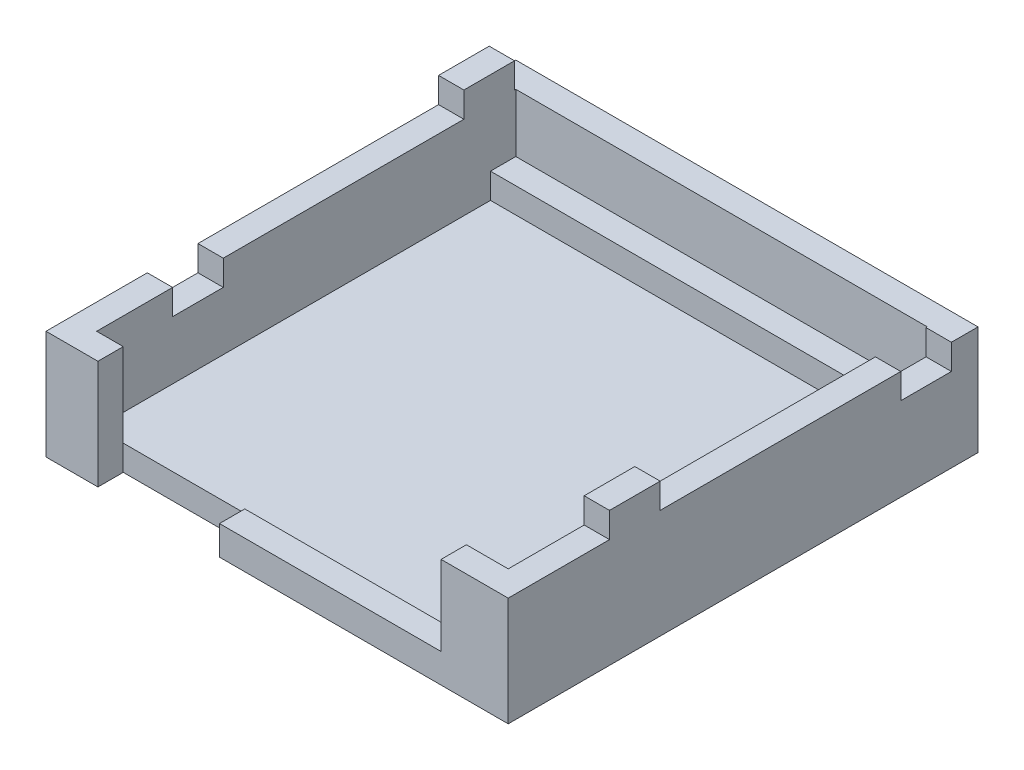
SolidWorks part; units mm, degrees
ref_plane "Front Plane" through (0, 0, 0) normal (0, 0, 1) x (1, 0, 0)
ref_plane "Top Plane" through (0, 0, 0) normal (0, 1, 0) x (1, 0, 0)
ref_plane "Right Plane" through (0, 0, 0) normal (1, 0, 0) x (0, 0, -1)
sketch "Sketch3" plane through (0, 0, 0) normal (0, 1, 0) x (1, 0, 0)
  line L1 (0, 0) -> (36.5, 0)
  line L2 (0, 0) -> (0, -37.1)
  line L3 (0, -37.1) -> (36.5, -37.1)
  line L4 (36.5, 0) -> (36.5, -37.1)
  dimension "D1" = 37.1
  dimension "D2" = 36.5
extrude "Shell" add sketch "Sketch3" along normal blind 8.6
sketch "Sketch4" plane through (0, 8.6, 0) normal (0, 1, 0) x (1, 0, 0)
  line L0 (36.5, 0) -> (0, 0) construction
  line L1 (2, -4) -> (34.5, -4)
  line L2 (2, -4) -> (2, -35.1)
  line L3 (2, -35.1) -> (34.5, -35.1)
  line L4 (34.5, -4) -> (34.5, -35.1)
  line L5 (36.5, -37.1) -> (36.5, 0) construction
  line L6 (0, 0) -> (0, -37.1) construction
  line L7 (0, -37.1) -> (36.5, -37.1) construction
  dimension "D1" = 4
  dimension "D2" = 2
  dimension "D3" = 2
  dimension "D4" = 2
extrude "Main Cavity" cut sketch "Sketch4" against normal offset from surface (6.6 mm away) 2 up to face at (18.25, 0, 18.55)
sketch "Sketch5" plane through (0, 8.6, 0) normal (0, 1, 0) x (1, 0, 0)
  line L0 (34.5, -35.1) -> (34.5, -4) construction
  line L1 (2, -4) -> (34.5, -4)
  line L2 (2, -4) -> (2, -2)
  line L3 (2, -2) -> (34.5, -2)
  line L4 (34.5, -4) -> (34.5, -2)
  dimension "D1" = 2
extrude "Support Shelf" cut sketch "Sketch5" against normal offset from surface (4.6 mm away) 2 up to face at (18.25, 2, 19.55)
sketch "Sketch6" plane through (0, 0, 37.1) normal (0, 0, 1) x (1, 0, 0)
  line L0 (0, 0) -> (36.5, 0) construction
  line L2 (31.2, 2.3) -> (31.2, 8.6)
  line L10 (13.7, 0) -> (4.1, 0)
  line L13 (4.1, 0) -> (4.1, 8.6)
  line L14 (0, 8.6) -> (0, 0) construction
  line L18 (13.7, 0) -> (13.7, 2.3)
  line L19 (13.7, 2.3) -> (31.2, 2.3)
  line L20 (31.2, 8.6) -> (4.1, 8.6)
  dimension "D1" = 4.1
  dimension "D6" = 9.6
extrude "Terminal Input" cut sketch "Sketch6" against normal up to surface (2 mm away) up to face at (18.25, 5.3, 35.1)
sketch "Sketch7" plane through (0, 8.6, 0) normal (0, 1, 0) x (1, 0, 0)
  line L0 (36.5, -37.1) -> (36.5, 0) construction
  line L1 (34.5, -25.1) -> (36.5, -25.1)
  line L2 (34.5, -25.1) -> (34.5, -29.1)
  line L3 (34.5, -29.1) -> (36.5, -29.1)
  line L4 (36.5, -25.1) -> (36.5, -29.1)
  line L5 (0, -2.1) -> (2, -2.1)
  line L6 (0, -2.1) -> (0, -6.1)
  line L7 (0, -6.1) -> (2, -6.1)
  line L8 (2, -2.1) -> (2, -6.1)
  line L9 (34.5, -35.1) -> (34.5, -2) construction
  line L10 (2, -2) -> (2, -35.1) construction
  line L11 (0, 0) -> (0, -37.1) construction
  line L12 (31.2, -37.1) -> (36.5, -37.1) construction
  line L14 (36.5, 0) -> (0, 0) construction
  dimension "D1" = 4
  dimension "D2" = 4
  dimension "D3" = 8
  dimension "D4" = 2.1
extrude "Male Tabs" add sketch "Sketch7" along normal blind 2
sketch "Sketch8" plane through (0, 8.6, 0) normal (0, 1, 0) x (1, 0, 0)
  line L0 (2, -2.1) -> (0, -2.1) construction
  line L1 (34.5, -2.1) -> (36.5, -2.1)
  line L2 (34.5, -2.1) -> (34.5, -6.1)
  line L3 (34.5, -6.1) -> (36.5, -6.1)
  line L4 (36.5, -2.1) -> (36.5, -6.1)
  line L5 (0, -25.1) -> (2, -25.1)
  line L6 (0, -25.1) -> (0, -29.1)
  line L7 (0, -29.1) -> (2, -29.1)
  line L8 (2, -25.1) -> (2, -29.1)
  line L9 (36.5, -25.1) -> (36.5, 0) construction
  line L11 (34.5, -4) -> (34.5, -35.1) construction
  line L12 (0, -6.1) -> (0, -37.1) construction
  line L13 (2, -6.1) -> (2, -35.1) construction
  line L14 (34.5, -29.1) -> (36.5, -29.1) construction
  dimension "D1" = 4
  dimension "D2" = 4
extrude "Female Tabs" cut sketch "Sketch8" against normal blind 2
